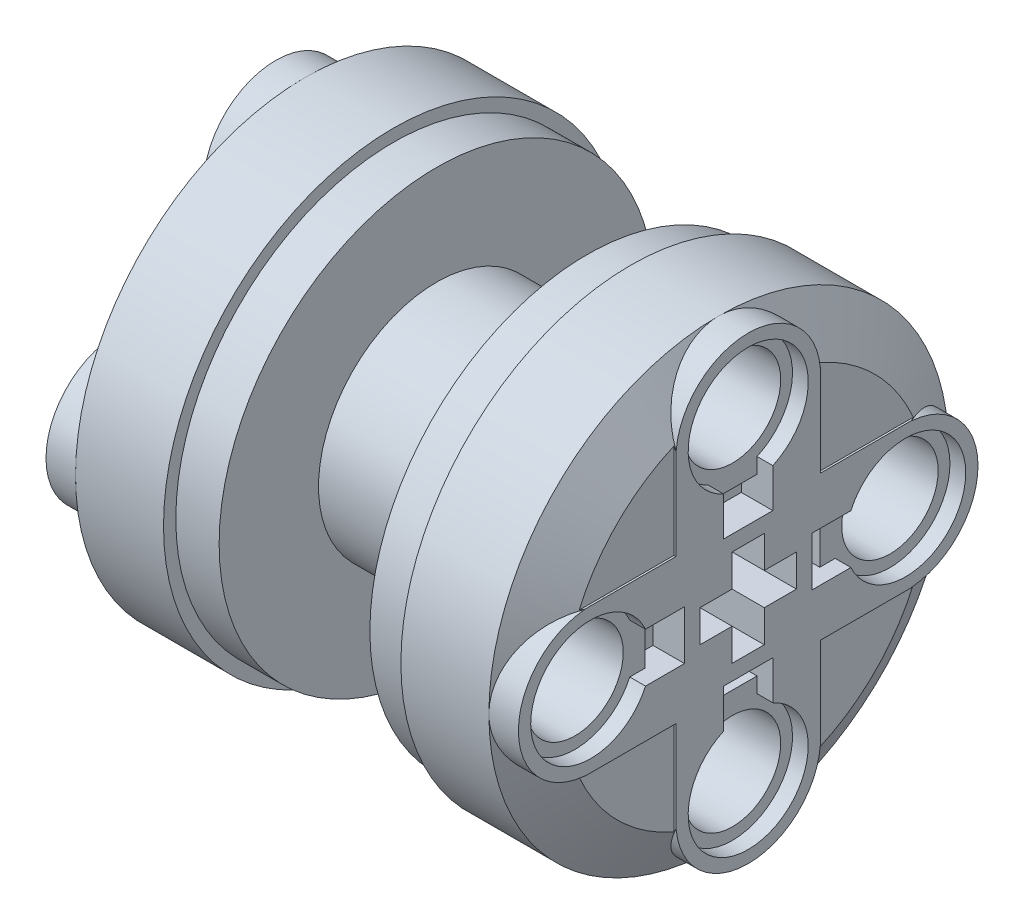
SolidWorks part; units mm, degrees
material "ABS"
ref_plane "Front Plane" through (0, 0, 0) normal (0, 0, 1) x (1, 0, 0)
ref_plane "Top Plane" through (0, 0, 0) normal (0, 1, 0) x (1, 0, 0)
ref_plane "Right Plane" through (0, 0, 0) normal (1, 0, 0) x (0, 0, -1)
ref_plane "Plane1" through (6.03, 0, 0) normal (1, 0, 0) x (0, 0, -1)
sketch "Sketch2" plane through (6.03, 0, 0) normal (1, 0, 0) x (0, 0, -1)
  circle A0 centre (0, 0) radius 11.675
  dimension "D1" = 23.35
extrude "Extrude1" add sketch "Sketch2" along normal blind 5.97
sketch "Sketch3" plane through (12, 0, 0) normal (1, 0, 0) x (0, 0, -1)
  line L0 (-0.8167, 2.45) -> (0.8167, 2.45)
  line L1 (0.8167, 2.45) -> (0.8167, 0.8167)
  line L2 (0.8167, 0.8167) -> (2.45, 0.8167)
  line L3 (2.45, 0.8167) -> (2.45, -0.8167)
  line L4 (2.45, -0.8167) -> (0.8167, -0.8167)
  line L5 (0.8167, -0.8167) -> (0.8167, -2.45)
  line L6 (0.8167, -2.45) -> (-0.8167, -2.45)
  line L7 (-0.8167, -2.45) -> (-0.8167, -0.8167)
  line L8 (-0.8167, -0.8167) -> (-2.45, -0.8167)
  line L9 (-2.45, -0.8167) -> (-2.45, 0.8167)
  line L10 (-2.45, 0.8167) -> (-0.8167, 0.8167)
  line L11 (-0.8167, 0.8167) -> (-0.8167, 2.45)
  line L12 (-0.8167, 0.8167) -> (0.8167, -0.8167) construction
  dimension "D1" = 4.9
  dimension "D2" = 1.6333
  dimension "D3" = 4.9
sketch "Sketch4" plane through (12, 0, 0) normal (1, 0, 0) x (0, 0, -1)
  line L0 (0, 8) -> (0, -8) construction
  line L1 (-8, 0) -> (8, 0) construction
  circle A0 centre (-8, 0) radius 2.45
  circle A1 centre (8, 0) radius 2.45
  circle A2 centre (0, 8) radius 2.45
  circle A3 centre (0, -8) radius 2.45
  dimension "D3" = 4.9
  dimension "D1" = 16
  dimension "D2" = 16
sketch "Sketch5" plane through (12, 0, 0) normal (1, 0, 0) x (0, 0, -1)
  circle A0 centre (-8, 0) radius 3.05
  circle A1 centre (-8, 0) radius 2.45 construction
  circle A2 centre (0, 8) radius 3.05
  circle A3 centre (0, 8) radius 2.45 construction
  circle A4 centre (0, -8) radius 3.05
  circle A5 centre (0, -8) radius 2.45 construction
  circle A6 centre (8, 0) radius 3.05
  circle A9 centre (8, 0) radius 2.45 construction
  dimension "D1" = 6.1
chamfer "Chamfer1" distance 1.5 angle 60 1 edges at (12, 0, -11.675) first distance on face at (12, 0, -11.675)
sketch "Sketch6" plane through (6.03, 0, 0) normal (1, 0, 0) x (0, 0, -1)
  circle A0 centre (-8, 0) radius 3.675
  circle A1 centre (0, 0) radius 11.675 construction
extrude "Extrude2" add sketch "Sketch6" along normal up to surface (5.97 mm away) up to face at (12, 0, -9.0769)
sketch "Sketch7" plane through (0, 0, 0) normal (0, 0, 1) x (1, 0, 0)
  line L0 (0, 0) -> (12, 0) construction
  line L1 (12, 0.8167) -> (12, -0.8167) construction
ref_axis "Axis1" through (12, 0, 0) along (-1, 0, 0)
pattern_circular "CirPattern2" count 4 over 360 about axis through (12, 0, 0) along (-1, 0, 0) of "Extrude2"
sketch "Sketch8" plane through (6.03, 0, 0) normal (-1, 0, 0) x (0, 0, 1)
  circle A0 centre (0, 0) radius 11.05
  circle A1 centre (8, 0) radius 3.05 construction
extrude "Extrude3" add sketch "Sketch8" along normal blind 2.2
extrude "Cut-Extrude1" cut sketch "Sketch4" against normal blind 8
extrude "Cut-Extrude2" cut sketch "Sketch5" against normal blind 0.8
sketch "Sketch10" plane through (12, 0, 0) normal (1, 0, 0) x (0, 0, -1)
  line L0 (-5.8929, 0) -> (-3.2365, 0) construction
  line L1 (-5.8929, 1.25) -> (-3.2365, 1.25)
  line L2 (-5.8929, 1.25) -> (-5.8929, -1.25)
  line L3 (-5.8929, -1.25) -> (-3.2365, -1.25)
  line L4 (-3.2365, 1.25) -> (-3.2365, -1.25)
  circle A0 centre (-8, 0) radius 2.45 construction
  dimension "D1" = 2.5
extrude "Cut-Extrude3" cut sketch "Sketch10" against normal blind 0.8
sketch "Sketch11" plane through (11.2, 0, 0) normal (1, 0, 0) x (0, 0, -1)
  line L0 (-5.2179, -1.25) -> (-3.2365, -1.25) construction
  line L1 (-3.2365, 1.25) -> (-4.4365, 1.25)
  line L2 (-3.2365, 1.25) -> (-3.2365, -1.25)
  line L3 (-3.2365, -1.25) -> (-4.4365, -1.25)
  line L4 (-4.4365, 1.25) -> (-4.4365, -1.25)
  dimension "D1" = 1.2
extrude "Cut-Extrude4" cut sketch "Sketch11" against normal blind 0.8
pattern_circular "CirPattern3" count 4 over 360 about axis through (12, 0, 0) along (-1, 0, 0) of "Cut-Extrude3", "Cut-Extrude4"
sketch "Sketch12" plane through (12, 0, 0) normal (1, 0, 0) x (0, 0, -1)
  line L0 (-3.675, 12.3921) -> (-3.675, 3.675)
  line L1 (-3.675, 3.675) -> (-12.7782, 3.675)
  arc A0 (-12.7782, 3.675) -> (-3.675, 12.3921) centre (-4.0529, 3.675) cw
  arc A1 (3.6623, 8.3053) -> (-3.6623, 8.3053) centre (0, 8) ccw construction
  arc A2 (-8.3053, 3.6623) -> (-8.3053, -3.6623) centre (-8, 0) ccw construction
extrude "Cut-Extrude5" cut sketch "Sketch12" against normal blind 0.1
pattern_circular "CirPattern4" count 4 over 360 about axis through (12, 0, 0) along (-1, 0, 0) of "Cut-Extrude5"
mirror "Mirror3" about plane through (0, 0, 0) normal (1, 0, 0) of bodies 111
sketch "Sketch13" plane through (3.83, 0, 0) normal (-1, 0, 0) x (0, 0, 1)
  circle A0 centre (0, 0) radius 6
  dimension "D1" = 12
extrude "Extrude5" add sketch "Sketch13" along normal up to surface (7.66 mm away) separate body up to face at (-3.83, 0, 11.05)
combine bodies "Combine1" operation type add bodies to combine 112 113 111
extrude "Cut-Extrude6" cut sketch "Sketch3" against normal through all
ref_plane "right_mate_plane" through (11.2, 0, 0) normal (1, 0, 0) x (0, 0, -1)
ref_plane "left_mate_plane" through (-11.2, 0, 0) normal (-1, 0, 0) x (0, 0, 1)
equation "\"D2@Sketch3\" = \"D1@Sketch3\" / 3"
